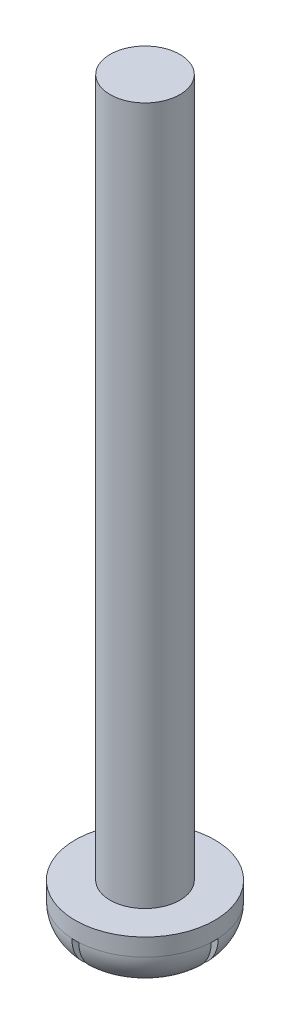
SolidWorks part; units mm, degrees
ref_plane "前视基准面" through (0, 0, 0) normal (0, 0, 1) x (1, 0, 0)
ref_plane "上视基准面" through (0, 0, 0) normal (0, 1, 0) x (1, 0, 0)
ref_plane "右视基准面" through (0, 0, 0) normal (1, 0, 0) x (0, 0, -1)
other "Configuration Table"
sketch "草图1" plane through (0, 0, 0) normal (0, 1, 0) x (1, 0, 0)
  circle A0 centre (0, 0) radius 2
  dimension "D1" = 4
extrude "凸台-拉伸1" add sketch "草图1" against normal blind 1.5
sketch "草图2" plane through (0, 0, 0) normal (0, 1, 0) x (1, 0, 0)
  circle A0 centre (0, 0) radius 1
  dimension "D1" = 2
extrude "凸台-拉伸2" add sketch "草图2" along normal blind 20 contours A0
sketch "草图4" plane through (0, -1.5, 0) normal (0, -1, 0) x (1, 0, 0)
  line L0 (-2, 0) -> (2, 0)
  line L1 (0, 2) -> (0, -2)
  circle A1 centre (0, 0) radius 2 construction
  point P2 (3, 0)
  point P9 (0, 3)
  point P10 (0, -3)
  point P11 (-3, 0)
extrude "切除-拉伸-薄壁1" cut sketch "草图4" against normal blind 1 and the other way through all thin thin type mid plane wall 0.2
ref_axis "基准轴1" through (0, 31.8772, 0) along (0, -1, 0)
fillet "圆角1" radius 1 4 edges at (1.4142, -1.5, 1.4142) (-1.4142, -1.5, 1.4142) (-1.4142, -1.5, -1.4142) (1.4142, -1.5, -1.4142)
